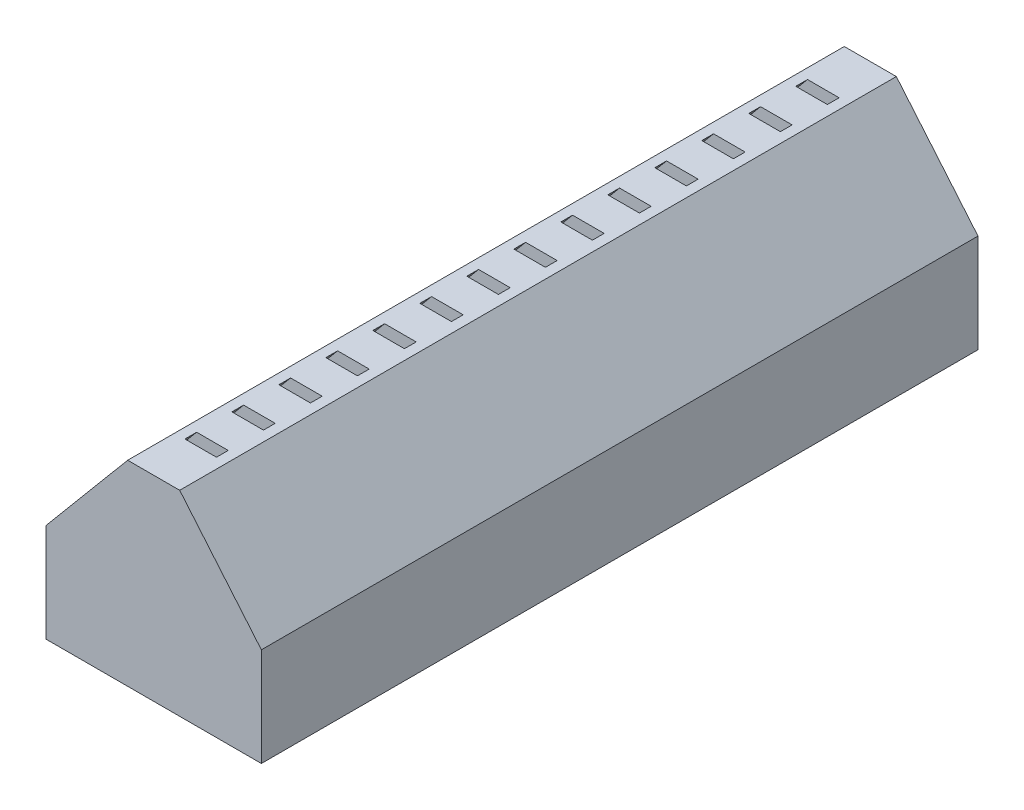
SolidWorks part; units mm, degrees
ref_plane "Ebene vorne" through (0, 0, 0) normal (0, 0, 1) x (1, 0, 0)
ref_plane "Ebene oben" through (0, 0, 0) normal (0, 1, 0) x (1, 0, 0)
ref_plane "Ebene rechts" through (0, 0, 0) normal (1, 0, 0) x (0, 0, -1)
sketch "Skizze3" plane through (0, 0, 0) normal (0, 0, 1) x (1, 0, 0)
  line L1 (0, 9.2) -> (0, -9.2) construction
  line L3 (-7.5, 0) -> (49992.5, 0) construction
  line L4 (-11, -3) -> (-11, 7.0579)
  line L5 (-11, 7.0579) -> (-2.6576, 17)
  line L6 (-2.6576, 17) -> (2.6576, 17)
  line L7 (2.6576, 17) -> (11, 7.0579)
  line L12 (0, 0) -> (8, 0) construction
  line L16 (11, 7.0579) -> (11, -3)
  line L18 (-11, -3) -> (11, -3)
  line L19 (8, 0) -> (8, 5.966) construction
  line L20 (8, 5.966) -> (0, 15.5) construction
  line L22 (0, 15.5) -> (-8, 5.966) construction
  line L23 (-8, 5.966) -> (-8, 0) construction
  line L24 (-8, 0) -> (0, 0) construction
  dimension "D2" = 22
  dimension "D3" = 3
  dimension "D4" = 1.5
  dimension "D5" = 20
  dimension "D1" = 50
  dimension "D6" = 3
  dimension "D7" = 3
extrude "Aufsatz-Linear austragen2" add sketch "Skizze3" along normal mid plane 3.6
sketch "Skizze2" plane through (0, 0, 0) normal (0, 0, 1) x (1, 0, 0)
  line L1 (0, 9) -> (0, -9) construction
  line L3 (-7.5, 0) -> (49992.5, 0) construction
  line L20 (-8, 0) -> (8, 0)
  line L21 (8, 0) -> (8, 5.966)
  line L22 (8, 5.966) -> (1.2586, 14)
  line L23 (1.2586, 14) -> (-1.2586, 14)
  line L24 (-1.2586, 14) -> (-8, 5.966)
  line L25 (-8, 5.966) -> (-8, 0)
  line L26 (-8, 0) -> (8, 0)
  line L27 (8, 0) -> (8, 5.966)
  line L28 (8, 5.966) -> (0, 15.5)
  line L30 (0, 15.5) -> (-8, 5.966)
  line L31 (-8, 5.966) -> (-8, 0)
  dimension "D1" = 3
extrude "Schnitt-Linear austragen1" cut sketch "Skizze2" against normal mid plane 1
sketch "Skizze5" plane through (0, 0, 0) normal (0, 0, 1) x (1, 0, 0)
  line L4 (-7.5519, 0) -> (-50007.5519, 0) construction
  line L5 (-8, 5.966) -> (-8, 0)
  line L6 (-8, 5.966) -> (-8, 0) construction
  line L7 (-8, 0) -> (8, 0)
  line L8 (-8, 0) -> (8, 0) construction
  line L9 (8, 0) -> (8, 5.966)
  line L15 (-0.75, 0) -> (0, 0.8938)
  line L16 (0, 0.8938) -> (0.75, 0)
  line L17 (0.75, 0) -> (-0.75, 0) construction
  line L18 (0, 0) -> (0, -50000) construction
  line L20 (8, 0) -> (8, 5.966) construction
  line L21 (8, 5.966) -> (0, 15.5)
  line L22 (8, 5.966) -> (0, 15.5) construction
  line L23 (0, 15.5) -> (-8, 5.966)
  line L24 (0, 15.5) -> (-8, 5.966) construction
  line L26 (-0.75, 0) -> (-0.75, -1.5)
  line L27 (-0.75, -1.5) -> (0.75, -1.5)
  line L28 (0.75, 0) -> (0.75, -1.5)
  dimension "D2" = 1.5
  dimension "D3" = 1.5
  dimension "D1" = 0
extrude "Schnitt-Linear austragen2" cut sketch "Skizze5" against normal through all both and the other way through all
sketch "Skizze6" plane through (0, 0, 1.8) normal (0, 0, 1) x (1, 0, 0)
  line L0 (0, 0) -> (0, -50000) construction
  line L1 (0, 0) -> (50000, 0) construction
  line L2 (2.6576, 17) -> (-2.6576, 17) construction
  line L21 (-2.6576, 17) -> (-1.6132, 17)
  line L22 (-2.6576, 17) -> (-11, 7.0579) construction
  line L23 (-1.6132, 17) -> (-10.2, 6.7667)
  line L24 (-10.2, 6.7667) -> (-10.2, 2)
  line L25 (-10.2, 2) -> (10.2, 2)
  line L26 (0, 2) -> (0, -3) construction
  line L27 (-11, -3) -> (11, -3) construction
  line L28 (11, -3) -> (-11, -3)
  line L29 (-11, -3) -> (-11, 7.0579)
  line L30 (-11, 7.0579) -> (-2.6576, 17)
  line L31 (11, 7.0579) -> (2.6576, 17)
  line L32 (11, -3) -> (11, 7.0579)
  line L33 (10.2, 6.7667) -> (10.2, 2)
  line L34 (1.6132, 17) -> (10.2, 6.7667)
  line L35 (2.6576, 17) -> (1.6132, 17)
  dimension "D1" = 0.8
  dimension "D2" = 0.8
  dimension "D3" = 2
extrude "Aufsatz-Linear austragen3" add sketch "Skizze6" along normal blind 1.2
pattern_linear "Lineares Muster1" count 15 spacing 4.8 along (0, 0, 1) of "Aufsatz-Linear austragen2", "Schnitt-Linear austragen1", "Schnitt-Linear austragen2", "Aufsatz-Linear austragen3"
sketch "Skizze8" plane through (0, 0, -1.8) normal (0, 0, -1) x (-1, 0, 0)
  line L9 (11, -3) -> (11, 7.0579)
  line L10 (11, 7.0579) -> (2.6576, 17)
  line L11 (2.6576, 17) -> (-2.6576, 17)
  line L12 (-2.6576, 17) -> (-11, 7.0579)
  line L13 (-11, 7.0579) -> (-11, -3)
  line L15 (-11, -3) -> (11, -3)
  line L17 (11, -3) -> (11, 7.0579)
  line L18 (11, 7.0579) -> (2.6576, 17)
  line L19 (2.6576, 17) -> (-2.6576, 17)
  line L20 (-2.6576, 17) -> (-11, 7.0579)
  line L21 (-11, 7.0579) -> (-11, -3)
  line L23 (-11, -3) -> (11, -3)
  dimension "D1" = 0
extrude "Aufsatz-Linear austragen4" add sketch "Skizze8" along normal blind 1.2 and the other way blind 1.3
sketch "Skizze9" plane through (0, 0, 69) normal (0, 0, 1) x (1, 0, 0)
  line L9 (1.6132, 17) -> (-1.6132, 17)
  line L10 (1.6132, 17) -> (-1.6132, 17)
  line L14 (-1.6132, 17) -> (-10.2, 6.7667)
  line L15 (-1.6132, 17) -> (-10.2, 6.7667)
  line L32 (-10.2, 6.7667) -> (-10.2, 2)
  line L33 (-10.2, 6.7667) -> (-10.2, 2)
  line L36 (-10.2, 2) -> (10.2, 2)
  line L37 (-10.2, 2) -> (10.2, 2)
  line L38 (10.2, 2) -> (10.2, 6.7667)
  line L39 (10.2, 2) -> (10.2, 6.7667)
  line L40 (10.2, 6.7667) -> (1.6132, 17)
  line L41 (10.2, 6.7667) -> (1.6132, 17)
  dimension "D1" = 0
extrude "Aufsatz-Linear austragen5" add sketch "Skizze9" along normal blind 1.2 and the other way blind 0.8
sketch "Skizze12" plane through (0, 0, 70.2) normal (0, 0, 1) x (1, 0, 0)
  line L8 (-0.75, -1.5) -> (-0.75, 0) construction
  line L9 (0.75, -1.5) -> (-0.75, -1.5) construction
  line L10 (0.75, 0) -> (0.75, -1.5) construction
  line L11 (0, 0.8938) -> (0.75, 0) construction
  line L12 (-0.75, 0) -> (0, 0.8938) construction
  line L13 (-0.75, -1.5) -> (-0.75, 0)
  line L14 (0.75, -1.5) -> (-0.75, -1.5)
  line L15 (0.75, 0) -> (0.75, -1.5)
  line L16 (0, 0.8938) -> (0.75, 0)
  line L17 (-0.75, 0) -> (0, 0.8938)
extrude "Aufsatz-Linear austragen7" add sketch "Skizze12" against normal up to vertex (3.5 mm away)
